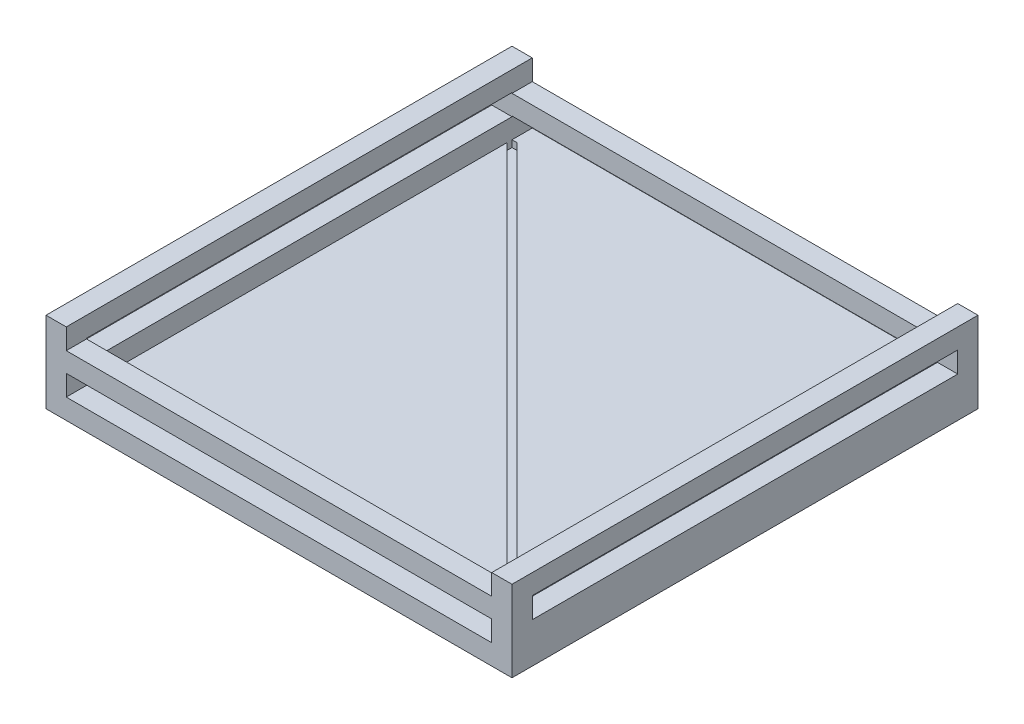
SolidWorks part; units mm, degrees
ref_plane "Front Plane" through (0, 0, 0) normal (0, 0, 1) x (1, 0, 0)
ref_plane "Top Plane" through (0, 0, 0) normal (0, 1, 0) x (1, 0, 0)
ref_plane "Right Plane" through (0, 0, 0) normal (1, 0, 0) x (0, 0, -1)
sketch "Sketch1" plane through (0, 0, 0) normal (0, 1, 0) x (1, 0, 0)
  line L0 (-57.5, 57.5) -> (57.5, -57.5) construction
  line L1 (-57.5, 57.5) -> (57.5, 57.5)
  line L2 (-57.5, 57.5) -> (-57.5, -57.5)
  line L3 (-57.5, -57.5) -> (57.5, -57.5)
  line L4 (57.5, 57.5) -> (57.5, -57.5)
  line L5 (57.5, 57.5) -> (-57.5, -57.5) construction
  point P4 (0, 0)
  dimension "D1" = 115
  dimension "D2" = 115
extrude "Base" add sketch "Sketch1" along normal blind 5
sketch "Sketch2" plane through (-57.5, 0, 0) normal (-1, 0, 0) x (0, 0, 1)
  line L0 (-52.5, 15.08) -> (-52.5, 20) construction
  line L1 (-57.5, 5) -> (57.5, 5)
  line L2 (-57.5, 5) -> (-57.5, 20)
  line L3 (-57.5, 20) -> (57.5, 20)
  line L4 (57.5, 5) -> (57.5, 20)
  line L5 (-52.5, 9.92) -> (52.5, 9.92)
  line L6 (-52.5, 9.92) -> (-52.5, 15.08)
  line L7 (-52.5, 15.08) -> (52.5, 15.08)
  line L8 (52.5, 9.92) -> (52.5, 15.08)
  line L9 (-52.5, 15.08) -> (-57.5, 15.08) construction
  line L10 (-52.5, 9.92) -> (-52.5, 5) construction
  line L11 (-52.5, 9.92) -> (-57.5, 9.92) construction
  line L12 (52.5, 15.08) -> (52.5, 20) construction
  line L13 (52.5, 15.08) -> (57.5, 15.08) construction
  line L14 (52.5, 9.92) -> (57.5, 9.92) construction
  line L15 (52.5, 9.92) -> (52.5, 5) construction
  line M15 (57.5, 5) -> (-57.5, 5)
  dimension "D1" = 4.92
  dimension "D2" = 4.92
  dimension "D4" = 5
  dimension "D5" = 15
sketch "Sketch4" plane through (0, 0, -57.5) normal (0, 0, -1) x (-1, 0, 0)
  line L0 (57.5, 5) -> (57.5, 20) construction
  line L1 (-57.5, 5) -> (-52.5, 5)
  line L2 (-57.5, 5) -> (-57.5, 20)
  line L3 (-57.5, 20) -> (-52.5, 20)
  line L4 (57.5, 5) -> (57.5, 20)
  line L5 (57.5, 15.08) -> (57.5, 20) construction
  line L6 (52.5, 14.92) -> (52.5, 20)
  line L7 (-52.5, 14.92) -> (52.5, 14.92)
  line L9 (-52.5, 10.08) -> (52.5, 10.08)
  line L11 (52.5, 14.92) -> (57.5, 14.92) construction
  line L12 (52.5, 10.08) -> (57.5, 10.08) construction
  line L13 (52.5, 10.08) -> (52.5, 5)
  line L14 (-52.5, 14.92) -> (-52.5, 20)
  line L15 (-52.5, 14.92) -> (-57.5, 14.92) construction
  line L16 (-52.5, 10.08) -> (-57.5, 10.08) construction
  line L17 (-52.5, 10.08) -> (-52.5, 5)
  line L18 (52.5, 20) -> (57.5, 20)
  line L19 (52.5, 5) -> (57.5, 5)
  dimension "D1" = 5.08
  dimension "D3" = 5.08
  dimension "D5" = 5
  dimension "D6" = 5
  dimension "D7" = 5
  dimension "D4" = 15
extrude "Frame1" add sketch "Sketch2" against normal up to vertex (5 mm away) contours L4 L3 L2 L8 L5 L6 L7 M15 region at (-57.5, 12.5, -56.3403) up to point (-52.5, 20, -57.5)
extrude "Frame2" add sketch "Sketch4" against normal up to vertex (5 mm away) contours L2 L3 L14 L7 L6 L18 L4 L19 L13 L9 L17 L1 up to point (-57.5, 15.08, -52.5)
extrude "Frame3" add sketch "Sketch2<4>" against normal up to surface (115 mm away) from surface up to face at (57.5, 8.3333, -17.5) starting at face at (52.5, 17.46, -55)
sketch "Sketch2<4>" plane through (-57.5, 0, 0) normal (-1, 0, 0) x (0, 0, 1) same geometry as "Sketch2"
extrude "Frame4" add sketch "Sketch4<3>" against normal up to surface (115 mm away) from surface up to face at (0, 11.25, 57.5) starting at face at (-55, 12.5, 52.5)
sketch "Sketch4<3>" plane through (0, 0, -57.5) normal (0, 0, -1) x (-1, 0, 0) same geometry as "Sketch4"
sketch "Sketch7" plane through (0, 5, 0) normal (0, 1, 0) x (1, 0, 0)
  line L0 (52.5, -51.2649) -> (-51.2649, 52.5)
  line L2 (52.5, 52.5) -> (-52.5, 52.5) construction
  line L4 (-52.5, 57.5) -> (-52.5, -57.5) construction
  line L5 (-52.5, 51.2649) -> (51.2649, -52.5)
  line L10 (-52.5, 51.2649) -> (-52.5, 52.5)
  line L11 (-52.5, 52.5) -> (-51.2649, 52.5)
  line L13 (52.5, -57.5) -> (52.5, 57.5) construction
  line L14 (52.5, -52.5) -> (-52.5, -52.5) construction
  line L15 (52.5, -51.2649) -> (52.5, -52.5)
  line L16 (52.5, -52.5) -> (51.2649, -52.5)
  dimension "D1" = 1.7467
extrude "Angled Track" cut sketch "Sketch7" against normal blind 1.67
equation "\"Frame side length\"= \"Useful Tray Size\" + \"Universal Bar Height\" * 3"
equation "\"D1@Sketch1\"=\"Frame side length\""
equation "\"D2@Sketch1\"=\"Frame side length\""
equation "\"Universal Bar Height\"= 5mm"
equation "\"D1@Base\" = \"Universal Bar Height\""
equation "\"D2@Sketch2\"=\"Universal Bar Height\"-\"Frame Tolerance\"/2"
equation "\"D3@Sketch2\"=\"Universal Bar Height\""
equation "\"D4@Sketch2\"=\"Universal Bar Height\""
equation "\"D5@Sketch4\"=\"Universal Bar Height\""
equation "\"D2@Sketch4\"=\"Universal Bar Height\""
equation "\"D6@Sketch4\"=\"Universal Bar Height\""
equation "\"D7@Sketch4\"=\"Universal Bar Height\""
equation "\"Useful Tray Size\"= 100mm"
equation "\"Frame Tolerance\"= 0.16mm'The total extra space on the top and bottom of the frames"
equation "\"D1@Sketch2\"=\"Universal Bar Height\"-\"Frame Tolerance\"/2"
equation "\"D5@Sketch2\"=\"Universal Bar Height\"*3"
equation "\"D1@Sketch4\"=\"Universal Bar Height\"+\"Frame Tolerance\"/2"
equation "\"D3@Sketch4\"=\"Universal Bar Height\"+\"Frame Tolerance\"/2"
equation "\"Track Tolerance\"= 0.08mm'The total extra width of the track"
equation "\"D1@Sketch7\"=\"Universal Bar Height\"/3 + \"Track Tolerance\""
